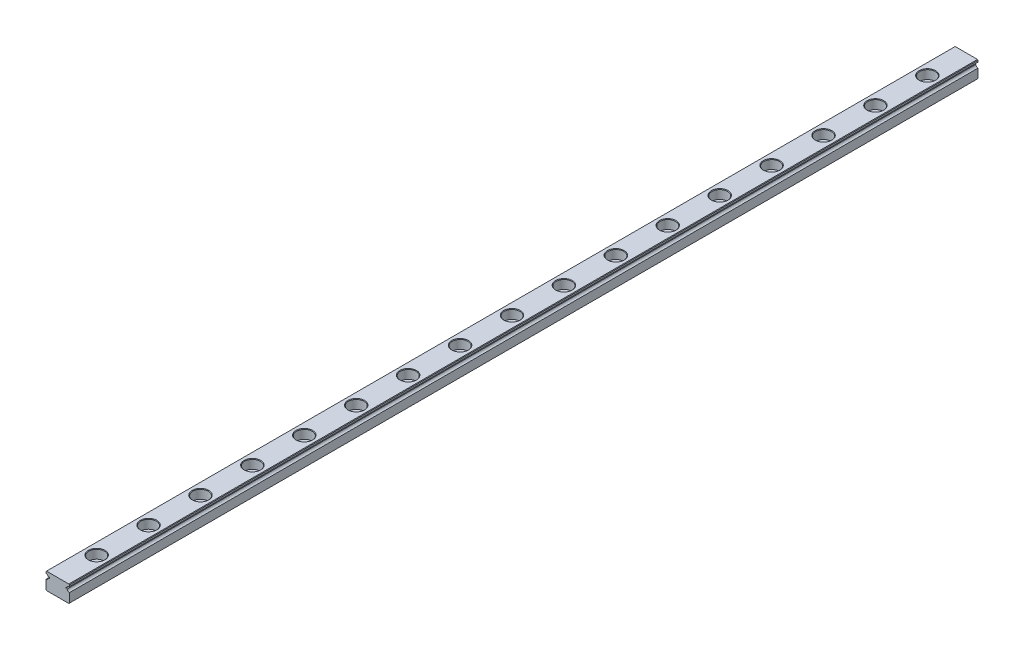
SolidWorks part; units mm, degrees
ref_plane "Спереди" through (0, 0, 0) normal (0, 0, 1) x (1, 0, 0)
ref_plane "Сверху" through (0, 0, 0) normal (0, 1, 0) x (1, 0, 0)
ref_plane "Справа" through (0, 0, 0) normal (1, 0, 0) x (0, 0, -1)
sketch "Sketch1" plane through (0, 0, 0) normal (0, 0, 1) x (1, 0, 0)
  line L0 (0, 0) -> (0, 4.3706) construction
  line L1 (-4.3, -3.25) -> (4.3, -3.25)
  line L2 (-4.5, -3.05) -> (-4.5, 0.455)
  line L3 (-4.3, 3.25) -> (4.3, 3.25)
  line L4 (4.5, -3.05) -> (4.5, 0.455)
  line L5 (-4.5, -3.25) -> (4.5, 3.25) construction
  line L6 (-4.5, 3.25) -> (4.5, -3.25) construction
  line L7 (-4.5, 2.445) -> (-4.5, 3.05)
  line L8 (4.5, 2.445) -> (4.5, 3.05)
  line L9 (-4.5, -3.05) -> (-4.3, -3.25)
  line L10 (4.3, -3.25) -> (4.5, -3.05)
  line L11 (4.3, 3.25) -> (4.5, 3.05)
  line L12 (-4.5, 3.05) -> (-4.3, 3.25)
  line L13 (3.6177, 1.2625) -> (3.1501, 1.2625)
  line L14 (-3.6177, 1.2625) -> (-3.1501, 1.2625)
  line L15 (3.1501, 1.2625) -> (3.1501, 1.7625)
  line L16 (-3.6501, 1.7625) -> (-3.1501, 1.7625)
  line L17 (-3.1501, 1.2625) -> (-3.1501, 1.7625)
  line L18 (3.6501, 1.7625) -> (3.1501, 1.7625)
  arc A0 (-4.5, 2.445) -> (-3.6501, 1.7625) centre (-4.6, 1.45) cw
  arc A1 (4.5, 2.445) -> (3.6501, 1.7625) centre (4.6, 1.45) ccw
  arc A2 (-3.6177, 1.2625) -> (-4.5, 0.455) centre (-4.6, 1.45) cw
  arc A3 (3.6177, 1.2625) -> (4.5, 0.455) centre (4.6, 1.45) ccw
  point P0 (0, 0)
  dimension "D4" = 1
  dimension "D5" = 0.1
  dimension "D1" = 9
  dimension "D2" = 6.5
  dimension "D3" = 1.8
  dimension "D6" = 0.5
  dimension "D7" = 0.5
extrude "Extrude1" add sketch "Sketch1" along normal blind 350
sketch "Sketch2" plane through (0, 3.25, 0) normal (0, 1, 0) x (1, 0, 0)
  line L0 (0, 0) -> (0, -15) construction
  circle A0 centre (0, -15) radius 1.75
  circle A1 centre (0, -15) radius 3
  dimension "D1" = 3.5
  dimension "D2" = 6
  dimension "D3" = 15
extrude "Extrude2" cut sketch "Sketch2" against normal up to next contours A0 region at (0, 3.25, 15)
extrude "Extrude4" cut sketch "Sketch" against normal blind 3.5
sketch "Sketch" plane through (0, 3.25, 0) normal (0, 1, 0) x (1, 0, 0) same geometry as "Sketch2"
chamfer "Chamfer1" distance 0.2 angle 45 2 edges at (0, -3.25, 16.75) (0, 3.25, 18)
pattern_linear "LPattern1" count 17 spacing 20 along (0, 0, 1) of "Extrude4", "Extrude2", "Chamfer1"
